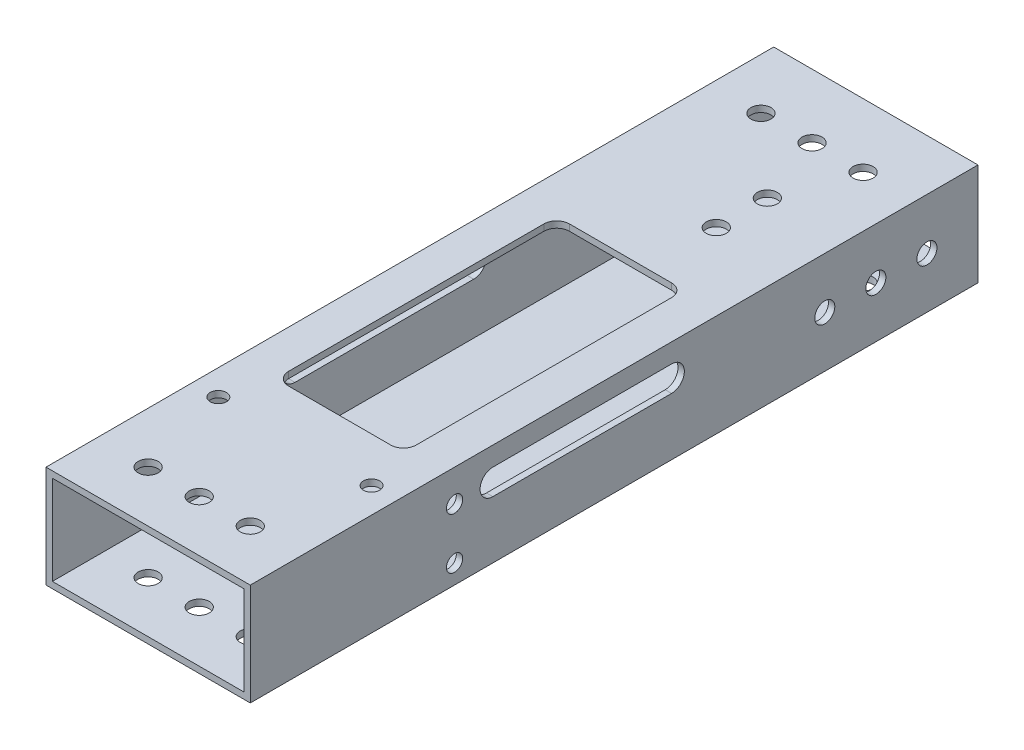
SolidWorks part; units mm, degrees
other "Markup4"
sketch "Sketch7" plane through (25.4, -12.7, 0) normal (0.9921, -0.1226, -0.0275) x (-0.1217, -0.992, 0.0335)
other "Markup5"
sketch "Sketch10"
material "6061-T6 (SS)"
ref_plane "Front Plane" through (0, 0, 0) normal (0, 0, 1) x (1, 0, 0)
ref_plane "Top Plane" through (0, 0, 0) normal (0, 1, 0) x (1, 0, 0)
ref_plane "Right Plane" through (0, 0, 0) normal (1, 0, 0) x (0, 0, -1)
sketch "Sketch1" plane through (0, 0, 0) normal (0, 0, 1) x (1, 0, 0)
  line L1 (-25.4, -12.7) -> (25.4, -12.7)
  line L2 (-25.4, -12.7) -> (-25.4, 12.7)
  line L3 (-25.4, 12.7) -> (25.4, 12.7)
  line L4 (25.4, -12.7) -> (25.4, 12.7)
  line L5 (-25.4, -12.7) -> (25.4, 12.7) construction
  line L6 (-25.4, 12.7) -> (25.4, -12.7) construction
  line L7 (-23.8125, -11.1125) -> (23.8125, -11.1125)
  line L8 (-23.8125, -11.1125) -> (-23.8125, 11.1125)
  line L9 (-23.8125, 11.1125) -> (23.8125, 11.1125)
  line L10 (23.8125, -11.1125) -> (23.8125, 11.1125)
  line L11 (-23.8125, -11.1125) -> (23.8125, 11.1125) construction
  line L12 (-23.8125, 11.1125) -> (23.8125, -11.1125) construction
  point P0 (0, 0)
  point P6 (0, 0)
  dimension "D1" = 50.8
  dimension "D2" = 25.4
  dimension "D3" = 1.5875
  dimension "D4" = 1.5875
extrude "Boss-Extrude1" add sketch "Sketch1" along normal blind 180.975
sketch "Sketch2" plane through (0, 12.7, 0) normal (0, 1, 0) x (1, 0, 0)
  line L0 (25.4, 0) -> (-25.4, 0) construction
  line L1 (-25.4, -180.975) -> (-25.4, 0) construction
  line L3 (25.4, -180.975) -> (-25.4, -180.975) construction
  circle A0 centre (-12.7, -15.875) radius 2.4892
  circle A1 centre (0, -15.875) radius 2.4892
  circle A2 centre (12.7, -15.875) radius 2.4892
  circle A3 centre (-12.7, -168.275) radius 2.4892
  circle A4 centre (0, -168.275) radius 2.4892
  circle A5 centre (12.7, -168.275) radius 2.4892
  circle A6 centre (6.35, -33.3375) radius 2.4892
  circle A7 centre (6.35, -46.0375) radius 2.4892
  dimension "D1" = 4.9784
  dimension "D2" = 15.875
  dimension "D3" = 12.7
  dimension "D4" = 12.7
  dimension "D5" = 12.7
  dimension "D6" = 12.7
  dimension "D7" = 31.75
  dimension "D8" = 33.3375
extrude "Cut-Extrude1" cut sketch "Sketch2" against normal through all
sketch "Sketch9" plane through (0, 12.7, 0) normal (0, 1, 0) x (1, 0, 0)
  line L0 (25.4, 0) -> (-25.4, 0) construction
  line L1 (-15.875, -63.5) -> (15.875, -63.5)
  line L2 (-15.875, -63.5) -> (-15.875, -133.35)
  line L3 (-15.875, -133.35) -> (15.875, -133.35)
  line L4 (15.875, -63.5) -> (15.875, -133.35)
  line L5 (-25.4, -180.975) -> (-25.4, 0) construction
  line L6 (-19.05, -144.4625) -> (19.05, -144.4625) construction
  line L7 (25.4, -180.975) -> (-25.4, -180.975) construction
  circle A0 centre (-19.05, -144.4625) radius 2.0193
  circle A1 centre (19.05, -144.4625) radius 2.0193
  point P14 (0, -180.975)
  point P15 (0, -144.4625)
  dimension "D6" = 4.0386
  dimension "D1" = 63.5
  dimension "D2" = 31.75
  dimension "D3" = 9.525
  dimension "D4" = 69.85
  dimension "D5" = 38.1
  dimension "D7" = 11.1125
extrude "Cut-Extrude2" cut sketch "Sketch9" against normal up to surface (23.8125 mm away) up to face at (0, -11.1125, 18.3642)
fillet "Fillet1" radius 3.175 4 edges at (-15.875, 11.9062, 63.5) (15.875, 11.9062, 133.35) (-15.875, 11.9062, 133.35) (15.875, 11.9062, 63.5)
sketch "Sketch11" plane through (0, 0, 0) normal (1, 0, 0) x (0, 0, -1)
  line L0 (-120.65, 4.7625) -> (-76.2, 4.7625) construction
  line L1 (-120.65, 7.9375) -> (-76.2, 7.9375)
  line L2 (-120.65, 1.5875) -> (-76.2, 1.5875)
  line L3 (-130.175, 12.7) -> (-66.675, 12.7) construction
  line L4 (-180.975, 12.7) -> (0, 12.7) construction
  line L5 (0, -12.7) -> (0, 12.7) construction
  arc A0 (-120.65, 7.9375) -> (-120.65, 1.5875) centre (-120.65, 4.7625) ccw
  arc A1 (-76.2, 1.5875) -> (-76.2, 7.9375) centre (-76.2, 4.7625) ccw
  circle A2 centre (-130.175, 4.7625) radius 2.0193
  circle A3 centre (-130.175, -7.9375) radius 2.0193
  circle A4 centre (-98.425, 4.7625) radius 9.525 construction
  circle A5 centre (-12.7, 0) radius 2.4892
  circle A6 centre (-25.4, 0) radius 2.4892
  circle A7 centre (-38.1, 0) radius 2.4892
  point P2 (-98.425, 4.7625)
  point P10 (-98.425, 12.7)
  dimension "D1" = 3.175
  dimension "D4" = 4.0386
  dimension "D6" = 19.05
  dimension "D8" = 4.9784
  dimension "D9" = 12.7
  dimension "D10" = 12.7
  dimension "D11" = 12.7
  dimension "D2" = 44.45
  dimension "D3" = 7.9375
  dimension "D5" = 9.525
  dimension "D7" = 12.7
extrude "Cut-Extrude3" cut sketch "Sketch11" against normal through all both and the other way through all
